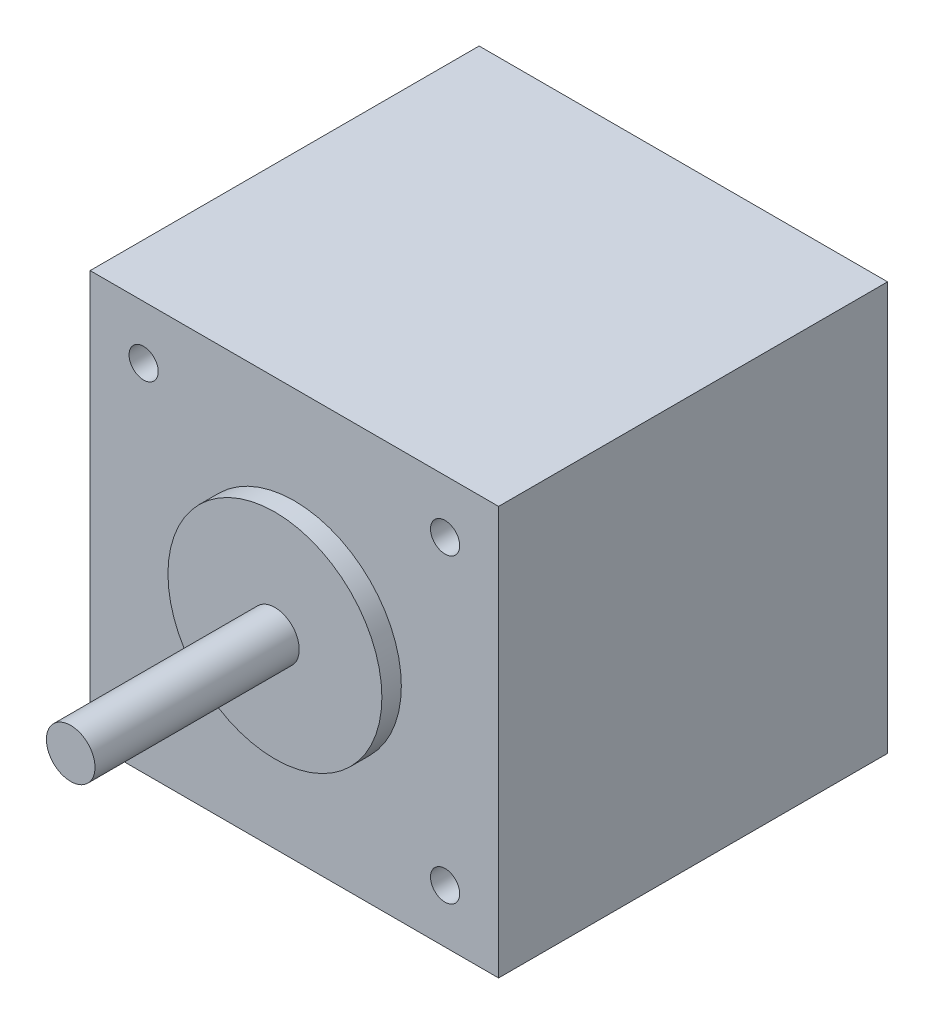
SolidWorks part; units mm, degrees
ref_plane "Спереди" through (0, 0, 0) normal (0, 0, 1) x (1, 0, 0)
ref_plane "Сверху" through (0, 0, 0) normal (0, 1, 0) x (1, 0, 0)
ref_plane "Справа" through (0, 0, 0) normal (1, 0, 0) x (0, 0, -1)
other "Configuration Table"
sketch "Эскиз1" plane through (0, 0, 0) normal (0, 0, 1) x (1, 0, 0)
  line L1 (-21, -21) -> (21, -21)
  line L2 (-21, -21) -> (-21, 21)
  line L3 (-21, 21) -> (21, 21)
  line L4 (21, -21) -> (21, 21)
  line L5 (-21, -21) -> (21, 21) construction
  line L6 (-21, 21) -> (21, -21) construction
  point P0 (0, 0)
  dimension "D1" = 42
  dimension "D2" = 42
extrude "Корпус" add sketch "Эскиз1" along normal blind 40
sketch "Эскиз2" plane through (0, 0, 0) normal (0, 0, 1) x (1, 0, 0)
  circle A0 centre (0, 0) radius 2.5
extrude "Вал_ПРЕДВ" add sketch "Эскиз2" along normal blind 63
sketch "Эскиз3" plane through (0, 0, 0) normal (0, 0, 1) x (1, 0, 0)
  circle A0 centre (0, 0) radius 11
  dimension "D1" = 22
extrude "Буртик_ПРЕДВ" add sketch "Эскиз3" along normal blind 42
sketch "Эскиз4" plane through (0, 0, 0) normal (0, 0, 1) x (1, 0, 0)
  circle A0 centre (-15.5, -15.5) radius 1.5
  circle A1 centre (-15.5, 15.5) radius 1.5
  circle A2 centre (15.5, -15.5) radius 1.5
  circle A3 centre (15.5, 15.5) radius 1.5
  dimension "D1" = 3
  dimension "D2" = 3
  dimension "D3" = 3
  dimension "D4" = 3
extrude "Крепеж_М3_ПРЕДВ" cut sketch "Эскиз4" against normal blind 4.5 from offset 40
equation "\"Мотор X ширина корпуса\"= 42.3"
equation "\"Мотор X высота корпуса\"= 42.3"
equation "\"Мотор X длина корпуса\"= 40"
equation "\"Мотор X вылет вала\"= 19.8"
equation "\"Мотор Y ширина корпуса\"= 42.3"
equation "\"Мотор Y высота корпуса\"= 42.3"
equation "\"Мотор Y длина корпуса\"= 48"
equation "\"Мотор Y вылет вала\"= 30"
equation "\"Мотор Z ширина корпуса\"= 42"
equation "\"Мотор Z высота корпуса\"= 42"
equation "\"Мотор Z длина корпуса\"= 40"
equation "\"Мотор Z вылет вала\"= 23"
equation "\"Мотор диаметр вала ПРЕДВ\"= 5"
equation "\"Мотор шаг крепления ПРЕДВ\"= 31"
equation "\"Мотор диаметр отверстий ПРЕДВ\"= 3"
equation "\"Мотор глубина отверстий ПРЕДВ\"= 4.5"
equation "\"Мотор диаметр буртика ПРЕДВ\"= 22"
equation "\"Мотор высота буртика ПРЕДВ\"= 2"
equation "\"Мотор диаметр шкива ПРЕДВ\"= 16"
equation "\"Мотор длина шкива ПРЕДВ\"= 12"
equation "\"Мотор отступ шкива ПРЕДВ\"= 5"
equation "\"Мотор X шаг градусов\"= 1.8"
equation "\"Мотор X ток А\"= 1.5"
equation "\"Мотор X сопротивление Ом\"= 1.3"
equation "\"Мотор X индуктивность мГн\"= 2"
equation "\"Мотор Y шаг градусов\"= 1.8"
equation "\"Мотор Y ток А\"= 2.2"
equation "\"Мотор Y сопротивление Ом\"= 0.9"
equation "\"Мотор Y индуктивность мГн\"= 2"
equation "\"Мотор Z шаг градусов\"= 1.8"
equation "\"Мотор Z ток А\"= 1"
equation "\"Мотор Z сопротивление Ом\"= 4"
equation "\"Мотор Z индуктивность мГн\"= 8"
equation "\"Мотор Y диаметр ротора\"= 25.78"
equation "\"D1@Эскиз1\" = \"Мотор Z ширина корпуса\""
equation "\"D2@Эскиз1\" = \"Мотор Z высота корпуса\""
equation "\"D1@Корпус\" = \"Мотор Z длина корпуса\""
equation "\"D1@Эскиз2\" = \"Мотор диаметр вала ПРЕДВ\""
equation "\"D1@Вал_ПРЕДВ\" = \"Мотор Z длина корпуса\" + \"Мотор Z вылет вала\""
equation "\"D1@Эскиз3\" = \"Мотор диаметр буртика ПРЕДВ\""
equation "\"D1@Буртик_ПРЕДВ\" = \"Мотор Z длина корпуса\" + \"Мотор высота буртика ПРЕДВ\""
equation "\"D1@Эскиз4\" = \"Мотор диаметр отверстий ПРЕДВ\""
equation "\"D2@Эскиз4\" = \"Мотор диаметр отверстий ПРЕДВ\""
equation "\"D3@Эскиз4\" = \"Мотор диаметр отверстий ПРЕДВ\""
equation "\"D4@Эскиз4\" = \"Мотор диаметр отверстий ПРЕДВ\""
equation "\"D1@Крепеж_М3_ПРЕДВ\" = \"Мотор глубина отверстий ПРЕДВ\""
equation "\"D19@Крепеж_М3_ПРЕДВ\" = \"Мотор Z длина корпуса\""
equation "\"Ширина груза\"= 420"
equation "\"Глубина груза\"= 490"
equation "\"Высота груза\"= 297"
equation "\"Ширина ячейки\"= \"Ширина груза\" + 10"
equation "\"Глубина ячейки\"= \"Глубина груза\" + 10"
equation "\"Высота ячейки\"= \"Высота груза\" + 10 + 13"
equation "\"Колво ячеек ширина\"= 2"
equation "\"Колво ячеек высота\"= 2"
equation "\"Толщина стенки\" = 6"
equation "\"Крепление дверцы\"= 5 "
equation "\"Ширина рейки\"= \"Толщина шестерни\""
equation "\"Высота рейки\"= 20"
equation "\"Высота пола\"= \"Толщина стенки\" * 2"
equation "\"Колво полозьев\"= 5"
equation "\"Отступ рейки\"= 20"
equation "\"Глубина каретки\"= \"Глубина ячейки\" + 30 + \"Мотор Y высота корпуса\" + 20"
equation "\"Отступ шпильки\"= 26"
equation "\"Диаметр шпильки\"= 5"
equation "\"Длинна шпильки\"= ( \"Высота ячейки\" + \"Толщина стенки\" + \"Высота пола\" ) * \"Колво ячеек высота\" + ( \"Толщина стенки\" + \"Отступ рейки\" ) * 2 "
equation "\"Ширина пластины\"= 50  "
equation "\"Высота зона выгрузки\"= \"Высота ячейки\" * 2 + \"Толщина стенки\" * 2"
equation "\"Колво выгрузки\"= 1"
equation "\"Отступ крепления мотора фиксации\" = (\"Ширина пластины\" + 20 - \"Толщина стенки\") / 2"
equation "\"Диаметр оси\"= 10"
equation "\"Диаметр ролика\"= 20"
equation "\"Колво роликов\"= 10"
equation "\"Шаг роликов\"= \"Диаметр ролика\" + 20"
equation "\"Ширина ячейки выгрузки\"= \"Ширина ячейки\" + \"Толщина стенки\" + \"Отступ крепления мотора фиксации\"*2"
equation "\"Длинна рейки\" = (\"Ширина ячейки\" + \"Толщина стенки\" + \"Крепление дверцы\") * \"Колво ячеек ширина\" + \"Ширина ячейки выгрузки\" * \"Колво выгрузки\" + \"Толщина стенки\" + \"Отступ крепления мотора фиксации\" * 2 - \"Крепление дверцы\" * \"Колво ячеек ширина\""
